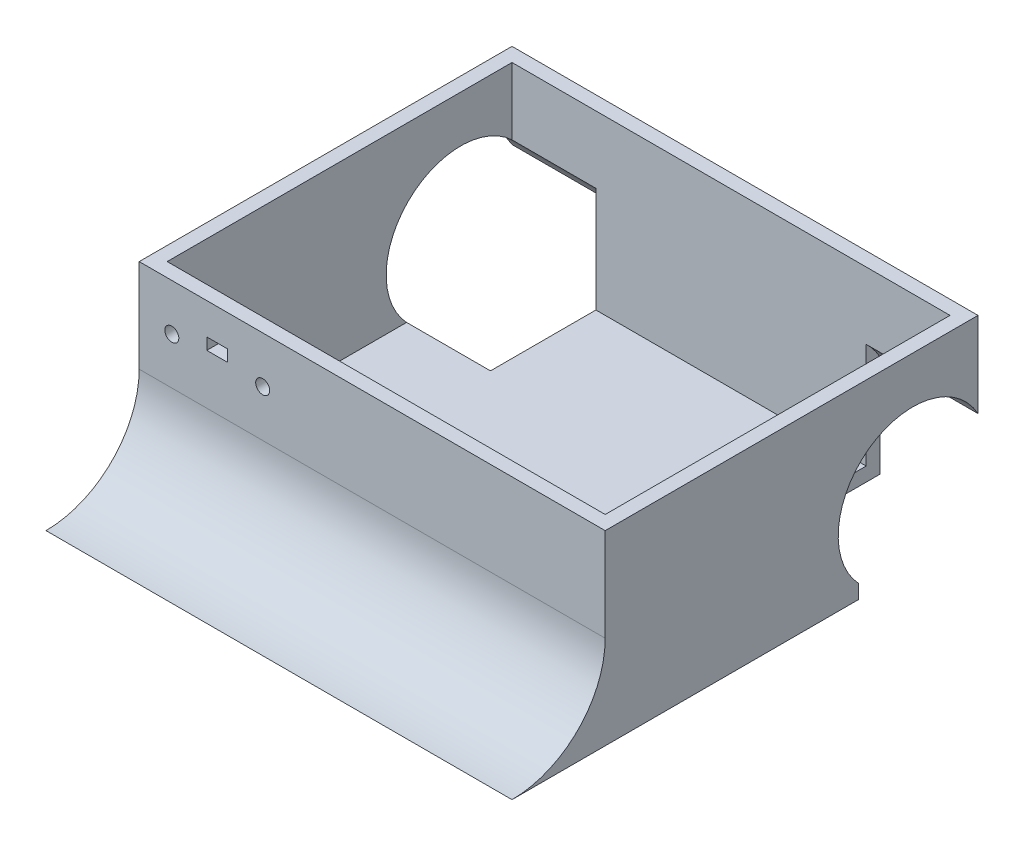
SolidWorks part; units mm, degrees
ref_plane "Plano frontal" through (0, 0, 0) normal (0, 0, 1) x (1, 0, 0)
ref_plane "Plano superior" through (0, 0, 0) normal (0, 1, 0) x (1, 0, 0)
ref_plane "Plano direito" through (0, 0, 0) normal (1, 0, 0) x (0, 0, -1)
sketch "Esboço1" plane through (0, 0, 0) normal (0, 1, 0) x (1, 0, 0)
  line L1 (-50, -50) -> (50, -50)
  line L2 (-50, -50) -> (-50, 50)
  line L3 (-50, 50) -> (50, 50)
  line L4 (50, -50) -> (50, 50)
  line L5 (-50, -50) -> (50, 50) construction
  line L6 (-50, 50) -> (50, -50) construction
  point P0 (0, 0)
  dimension "D1" = 100
  dimension "D2" = 100
extrude "Ressalto-extrusão1" add sketch "Esboço1" along normal mid plane 40
sketch "Esboço2" plane through (0, 0, 0) normal (1, 0, 0) x (0, 0, -1)
  line L0 (-50, 20) -> (-50, -20) construction
  line L1 (-50, 20) -> (-30, 20)
  line L2 (-50, 20) -> (50, 20) construction
  line L3 (-30, 20) -> (-30, 0)
  circle A0 centre (-50, 0) radius 20
extrude "Corte-extrusão1" cut sketch "Esboço2" against normal through all both and the other way through all contours A0 L3 L1 | A0 region at (0, 15.5326, 34.4674) region at (0, 0, 50)
sketch "Esboço3" plane through (0, 0, 0) normal (0, 1, 0) x (1, 0, 0)
  line L0 (-50, 50) -> (-50, -30) construction
  line L1 (-47, 47) -> (47, 47)
  line L2 (-47, 47) -> (-47, -27)
  line L3 (-47, -27) -> (47, -27)
  line L4 (47, 47) -> (47, -27)
  line L5 (-47, 47) -> (47, -27) construction
  line L6 (-47, -27) -> (47, 47) construction
  line L7 (50, 50) -> (-50, 50) construction
  line L8 (50, -30) -> (50, 50) construction
  line L9 (-50, -30) -> (50, -30) construction
  point P0 (0, 10)
  dimension "D1" = 3
  dimension "D2" = 3
  dimension "D3" = 3
  dimension "D4" = 3
extrude "Corte-extrusão2" cut sketch "Esboço3" along normal through all
sketch "Esboço5" plane through (0, 0, 0) normal (0, 1, 0) x (1, 0, 0)
  line L1 (-47, 47) -> (47, 47)
  line L2 (-47, 47) -> (-47, -27)
  line L3 (-47, -27) -> (47, -27)
  line L4 (47, 47) -> (47, -27)
extrude "Corte-extrusão3" cut sketch "Esboço5" against normal offset from surface (17 mm away) 3 up to face at (0, -20, 0)
sketch "Esboço6" plane through (0, 0, 0) normal (1, 0, 0) x (0, 0, -1)
  line L0 (47, -20) -> (47, -17) construction
  line L1 (-50, -20) -> (50, -20) construction
  line L2 (50, 20) -> (50, -20) construction
  line L3 (35.0734, -7) -> (47, -7) construction
  line L4 (35.0734, -7) -> (35.0734, -17) construction
  line L5 (35.0734, -17) -> (47, -17) construction
  line L6 (47, -7) -> (47, -17) construction
  line L7 (35.0734, -7) -> (47, -17) construction
  line L8 (35.0734, -17) -> (47, -7) construction
  line L9 (36, -22) -> (52, -22)
  line L10 (52, -22) -> (52, -6)
  circle A0 centre (36, -6) radius 16
  point P5 (41.0367, -12)
  dimension "D5" = 32
  dimension "D7" = 14
  dimension "D1" = 3
  dimension "D2" = 3
  dimension "D3" = 10
  dimension "D4" = 11.9266
  dimension "D6" = 14
extrude "Corte-extrusão4" cut sketch "Esboço6" against normal blind 21 from surface contours A0 | A0 L9 L10 region at (0, -18.4261, -48.4261) region at (0, -6, -36) starting at face at (50, -0.8284, 1.1716)
extrude "Corte-extrusão5" cut sketch "Esboço6<4>" along normal blind 21 from surface contours A0 L9 L10 | A0 region at (0, -18.4261, -48.4261) region at (0, -6, -36) starting at face at (-50, -0.8284, 1.1716)
sketch "Esboço6<4>" plane through (0, 0, 0) normal (1, 0, 0) x (0, 0, -1) same geometry as "Esboço6"
sketch "Esboço7" plane through (0, 0, 0) normal (0, 1, 0) x (1, 0, 0)
  line L0 (-29, 24.381) -> (-50, 24.381)
  line L1 (-47, 24.381) -> (-29, 24.381) construction
  line L2 (-50, 50) -> (-50, -30) construction
  line L3 (-50, 24.381) -> (-50, 28.254)
  line L4 (-50, 28.254) -> (-29, 28.254)
  line L5 (-29, 28.254) -> (-29, 24.381)
  line L6 (50, -30) -> (50, 50) construction
  line L7 (29, 28.254) -> (50, 28.254)
  line L8 (29, 28.254) -> (29, 24.381)
  line L9 (29, 24.381) -> (50, 24.381)
  line L10 (50, 28.254) -> (50, 24.381)
extrude "Corte-extrusão6" cut sketch "Esboço7" against normal blind 21
sketch "Esboço8" plane through (0, 0, 0) normal (0, 0, 1) x (1, 0, 0)
  line L0 (-50, 20) -> (-50, 0) construction
  line L1 (-50, 20) -> (50, 20) construction
  line L3 (-35.5, 13.25) -> (-31, 13.25)
  line L4 (-35.5, 13.25) -> (-35.5, 10.75)
  line L5 (-35.5, 10.75) -> (-31, 10.75)
  line L6 (-31, 13.25) -> (-31, 10.75)
  line L7 (-35.5, 13.25) -> (-31, 10.75) construction
  line L8 (-35.5, 10.75) -> (-31, 13.25) construction
  circle A0 centre (-43, 10) radius 1.5
  circle A1 centre (-23.5, 10) radius 1.5
  point P0 (-33.25, 12)
  point P7 (0, 0)
  point P10 (0, 0)
  dimension "D1" = 3
  dimension "D2" = 19.5
  dimension "D3" = 9.75
  dimension "D4" = 0.75
  dimension "D5" = 7
  dimension "D6" = 10
  dimension "D7" = 2.5
  dimension "D8" = 4.5
extrude "Corte-extrusão8" cut sketch "Esboço8" along normal through all
